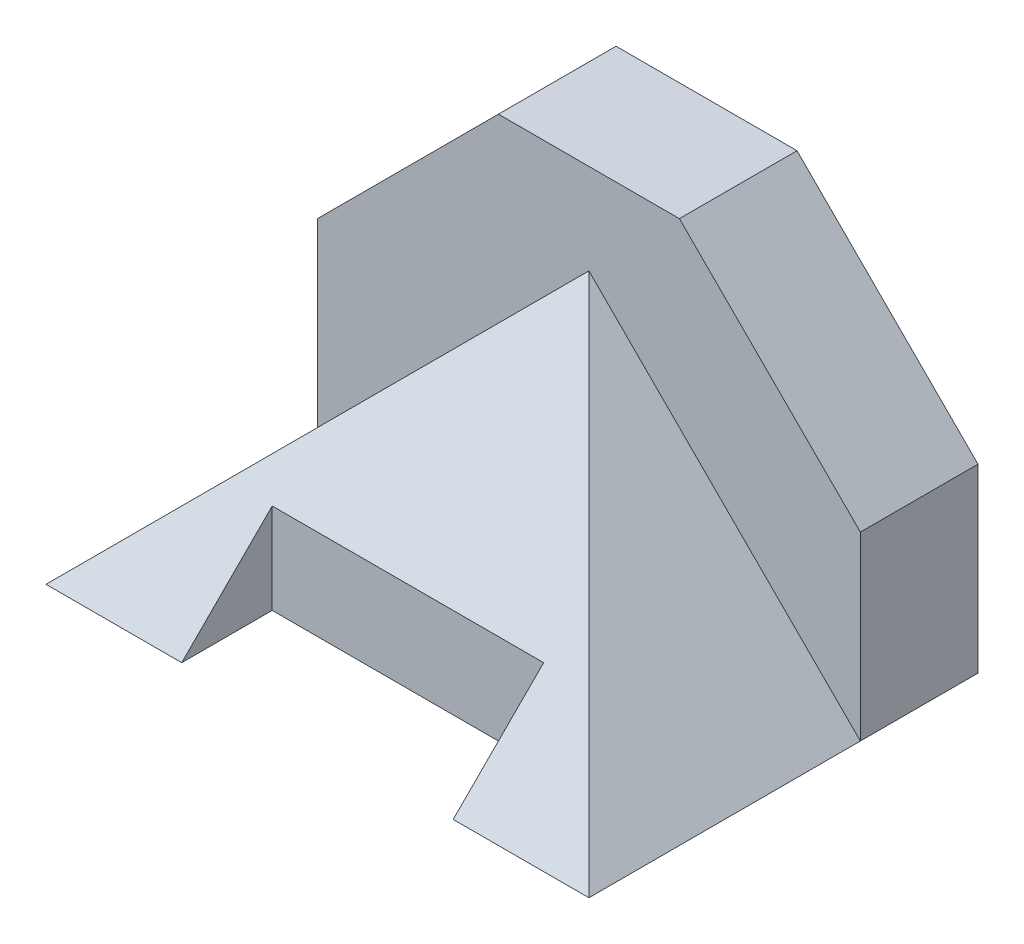
SolidWorks part; units mm, degrees
ref_plane "Front Plane" through (0, 0, 0) normal (0, 0, 1) x (1, 0, 0)
ref_plane "Top Plane" through (0, 0, 0) normal (0, 1, 0) x (1, 0, 0)
ref_plane "Right Plane" through (0, 0, 0) normal (1, 0, 0) x (0, 0, -1)
sketch "Sketch1" plane through (0, 0, 0) normal (0, 0, 1) x (1, 0, 0)
  line L0 (-76.2, 0) -> (76.2, 0)
  line L1 (76.2, 0) -> (76.2, 50.8)
  line L2 (76.2, 50.8) -> (25.4, 101.6)
  line L3 (25.4, 101.6) -> (-25.4, 101.6)
  line L4 (0, 101.6) -> (0, 0) construction
  line L5 (-76.2, 50.8) -> (-25.4, 101.6)
  line L6 (-76.2, 0) -> (-76.2, 50.8)
  line L7 (-76.2, 0) -> (0, 76.2)
  line L8 (0, 76.2) -> (76.2, 0)
  dimension "D1" = 76.2
  dimension "D2" = 50.8
  dimension "D3" = 25.4
  dimension "D4" = 101.6
extrude "Boss-Extrude1" add sketch "Sketch1" against normal blind 33.02 contours L4 L3 L5 L6 L7 | L3 L4 L8 L1 L2 | L8 L4 L0 | L4 L7 L0 region at (-25.4, 25.4, 0) region at (-40.7939, 59.2667, 0) region at (25.4, 25.4, 0) region at (40.7939, 59.2667, 0)
sketch "Sketch2" plane through (0, 0, 0) normal (0, 1, 0) x (1, 0, 0)
  line L0 (-76.2, 0) -> (-76.2, -76.2)
  line L1 (-76.2, -76.2) -> (-38.1, -76.2)
  line L2 (-38.1, -76.2) -> (-38.1, -50.8)
  line L3 (-38.1, -50.8) -> (38.1, -50.8)
  line L4 (0, -50.8) -> (0, 0) construction
  line L5 (38.1, -76.2) -> (38.1, -50.8)
  line L6 (76.2, -76.2) -> (38.1, -76.2)
  line L7 (76.2, 0) -> (76.2, -76.2)
  line L8 (-76.2, 0) -> (76.2, 0)
  dimension "D1" = 76.2
  dimension "D2" = 38.1
  dimension "D3" = 25.4
extrude "Boss-Extrude2" add sketch "Sketch2" along normal up to vertex (76.2 mm away) up to point (0, 76.2, 0)
extrude "Cut-Extrude1" cut sketch "Sketch1<5>" along normal up to next (76.2 mm away) contours L4 L3 L5 L6 L7 | L3 L4 L8 L1 L2 region at (-40.7939, 59.2667, 0) region at (40.7939, 59.2667, 0)
sketch "Sketch1<5>" plane through (0, 0, 0) normal (0, 0, 1) x (1, 0, 0) same geometry as "Sketch1"
sketch "Sketch6" plane through (0, 0, 0) normal (1, 0, 0) x (0, 0, -1)
  line L0 (-76.2, 0) -> (0, 76.2)
  line L1 (-76.2, 0) -> (-76.2, 76.2)
  line L2 (-76.2, 76.2) -> (0, 76.2)
extrude "Cut-Extrude2" cut sketch "Sketch6" against normal through all and the other way through all
